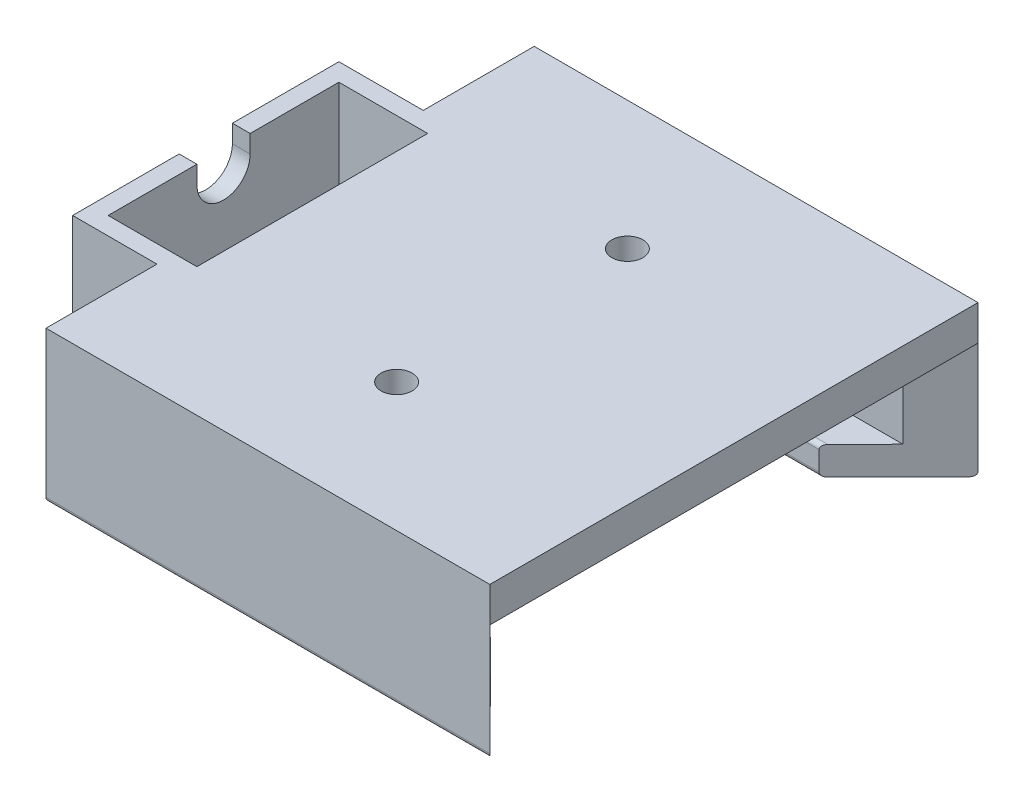
SolidWorks part; units mm, degrees
ref_plane "Спереди" through (0, 0, 0) normal (0, 0, 1) x (1, 0, 0)
ref_plane "Сверху" through (0, 0, 0) normal (0, 1, 0) x (1, 0, 0)
ref_plane "Справа" through (0, 0, 0) normal (1, 0, 0) x (0, 0, -1)
other "Configuration Table"
sketch "Эскиз1" plane through (0, 0, 0) normal (0, 1, 0) x (1, 0, 0)
  line L1 (-25, 27.5) -> (25, 27.5)
  line L2 (-25, 27.5) -> (-25, -27.5)
  line L3 (-25, -27.5) -> (25, -27.5)
  line L4 (25, 27.5) -> (25, -27.5)
  line L5 (-25, 27.5) -> (25, -27.5) construction
  line L6 (-25, -27.5) -> (25, 27.5) construction
  point P0 (0, 0)
  dimension "D1" = 55
  dimension "D2" = 50
extrude "Бобышка-Вытянуть1" add sketch "Эскиз1" along normal blind 6
sketch "Эскиз2" plane through (0, 0, 0) normal (0, -1, 0) x (1, 0, 0)
  line L0 (23.3173, 0) -> (43.7348, 0) construction
  line L1 (-25, 15) -> (-10, 15)
  line L2 (-25, 15) -> (-25, -15)
  line L3 (-25, -15) -> (-10, -15)
  line L4 (-10, 15) -> (-10, -15)
  line L5 (-25, -27.5) -> (-25, 27.5) construction
  line L6 (25, 27.5) -> (25, -27.5) construction
  dimension "D1" = 30
  dimension "D2" = 15
  dimension "D3" = 35
extrude "Бобышка-Вытянуть2" add sketch "Эскиз2" along normal blind 9
sketch "Эскиз3" plane through (0, -9, 0) normal (0, -1, 0) x (1, 0, 0)
  line L0 (-25, 15) -> (-25, -15) construction
  line L1 (-25, 12.5) -> (-10, 12.5)
  line L2 (-25, 12.5) -> (-25, 11.5)
  line L3 (-25, 11.5) -> (-10, 11.5)
  line L4 (-10, 12.5) -> (-10, 11.5)
  line L5 (-10, -15) -> (-10, 15) construction
  line L6 (-10, -15) -> (-10, 15) construction
  line L7 (-25, -11.5) -> (-10, -11.5)
  line L8 (-25, -11.5) -> (-25, -12.5)
  line L9 (-25, -12.5) -> (-10, -12.5)
  line L10 (-10, -11.5) -> (-10, -12.5)
  point P14 (-10, 0)
  point P15 (-10, -12)
  point P16 (-10, 12)
  dimension "D1" = 1
  dimension "D2" = 1
  dimension "D3" = 12
  dimension "D4" = 12
extrude "Вырез-Вытянуть1" cut sketch "Эскиз3" against normal blind 7
sketch "Эскиз4" plane through (0, 0, 0) normal (0, -1, 0) x (1, 0, 0)
  line L0 (-25, -27.5) -> (-25, -15) construction
  line L1 (-25, -23.25) -> (25, -23.25)
  line L2 (-25, -23.25) -> (-25, -27.5)
  line L3 (-25, -27.5) -> (25, -27.5)
  line L4 (25, -23.25) -> (25, -27.5)
  line L5 (25, 27.5) -> (25, -27.5) construction
  line L6 (-25, 15) -> (-25, 27.5) construction
  line L7 (-25, 23.25) -> (25, 23.25)
  line L8 (-25, 23.25) -> (-25, 27.5)
  line L9 (-25, 27.5) -> (25, 27.5)
  line L10 (25, 23.25) -> (25, 27.5)
  line L11 (0, 0) -> (45.721, 0) construction
  dimension "D1" = 46.5
extrude "Бобышка-Вытянуть3" add sketch "Эскиз4" along normal blind 9.5
sketch "Эскиз5" plane through (0, 0, 23.25) normal (0, 0, -1) x (-1, 0, 0)
  line L0 (25, 6) -> (25, -9.5) construction
  line L1 (-25, -9.5) -> (25, -9.5)
  line L2 (-25, -9.5) -> (-25, -5.8)
  line L3 (-25, -5.8) -> (25, -5.8)
  line L4 (25, -9.5) -> (25, -5.8)
  line L5 (-25, 0) -> (25, 0) construction
  dimension "D1" = 5.8
extrude "Бобышка-Вытянуть4" add sketch "Эскиз5" along normal blind 4.75
ref_plane "Плоскость1" through (0, 0, 0) normal (0, 0, 1) x (1, 0, 0)
mirror "Зеркальное отражение1" about plane through (0, 0, 0) normal (0, 0, 1) of "Бобышка-Вытянуть4"
sketch "Эскиз6" plane through (0, 0, 0) normal (0, -1, 0) x (1, 0, 0)
  line L0 (16.0877, -18.5) -> (25, -27.5)
  line L1 (25, -18.5) -> (-25, -18.5) construction
  line L2 (25, -27.5) -> (25, -18.5)
  line L3 (25, -18.5) -> (16.0877, -18.5)
  line L4 (8.525, 0) -> (-8.525, 0) construction
  line L5 (25, 18.5) -> (16.0877, 18.5)
  line L6 (25, 27.5) -> (25, 18.5)
  line L7 (16.0877, 18.5) -> (25, 27.5)
extrude "Вырез-Вытянуть2" cut sketch "Эскиз6" along normal blind 9.5
sketch "Эскиз7" plane through (-25, 0, 0) normal (-1, 0, 0) x (0, 0, 1)
  line L0 (-27.5, 6) -> (27.5, 6) construction
  line L1 (-15, -9) -> (15, -9)
  line L2 (-15, -9) -> (-15, 6)
  line L3 (-15, 6) -> (15, 6)
  line L4 (15, -9) -> (15, 6)
extrude "Бобышка-Вытянуть5" add sketch "Эскиз7" along normal blind 9.5
sketch "Эскиз8" plane through (0, 6, 0) normal (0, 1, 0) x (1, 0, 0)
  line L0 (-34.5, 15) -> (-25, 15) construction
  line L1 (-32.5, 13) -> (-22.5, 13)
  line L2 (-32.5, 13) -> (-32.5, -13)
  line L3 (-32.5, -13) -> (-22.5, -13)
  line L4 (-22.5, 13) -> (-22.5, -13)
  line L5 (-34.5, -15) -> (-34.5, 15) construction
  line L6 (-34.5, -15) -> (-25, -15) construction
  dimension "D1" = 2
  dimension "D2" = 2
  dimension "D3" = 2
  dimension "D4" = 12
extrude "Вырез-Вытянуть3" cut sketch "Эскиз8" against normal blind 10.5
sketch "Эскиз9" plane through (-34.5, 0, 0) normal (-1, 0, 0) x (0, 0, 1)
  line L0 (15, 6) -> (-15, 6) construction
  circle A0 centre (0, 6) radius 3
  dimension "D1" = 6
extrude "Вырез-Вытянуть4" cut sketch "Эскиз9" against normal blind 7.5
sketch "Эскиз10" plane through (0, 0, 0) normal (0, -1, 0) x (1, 0, 0)
  line L0 (8.525, 0) -> (-8.525, 0) construction
  circle A0 centre (0, 13) radius 1.75
  circle A1 centre (0, -13) radius 1.75
  dimension "D1" = 3.5
  dimension "D2" = 3.5
  dimension "D3" = 13
  dimension "D4" = 13
extrude "Вырез-Вытянуть5" cut sketch "Эскиз10" against normal blind 7.5
chamfer "Фаска1" distance 4 angle 45 2 edges at (0, 0, 11.25) (0, 0, -14.75)
sketch "Эскиз11" plane through (0, 6, 0) normal (0, 1, 0) x (1, 0, 0)
  line L16 (-34.5, 3) -> (-32.5, 3)
  line L17 (-32.5, 3) -> (-32.5, 13)
  line L18 (-32.5, 13) -> (-22.5, 13)
  line L19 (-22.5, 13) -> (-22.5, -13)
  line L20 (-22.5, -13) -> (-32.5, -13)
  line L21 (-32.5, -13) -> (-32.5, -3)
  line L22 (-32.5, -3) -> (-34.5, -3)
  line L23 (-34.5, -3) -> (-34.5, -15)
  line L24 (-34.5, -15) -> (-25, -15)
  line L25 (-25, -15) -> (-25, -27.5)
  line L26 (-25, -27.5) -> (25, -27.5)
  line L27 (25, -27.5) -> (25, 27.5)
  line L28 (25, 27.5) -> (-25, 27.5)
  line L29 (-25, 27.5) -> (-25, 15)
  line L30 (-25, 15) -> (-34.5, 15)
  line L31 (-34.5, 15) -> (-34.5, 3)
  line L32 (-34.5, 3) -> (-32.5, 3)
  line L33 (-32.5, 3) -> (-32.5, 13)
  line L34 (-32.5, 13) -> (-22.5, 13)
  line L35 (-22.5, 13) -> (-22.5, -13)
  line L36 (-22.5, -13) -> (-32.5, -13)
  line L37 (-32.5, -13) -> (-32.5, -3)
  line L38 (-32.5, -3) -> (-34.5, -3)
  line L39 (-34.5, -3) -> (-34.5, -15)
  line L40 (-34.5, -15) -> (-25, -15)
  line L41 (-25, -15) -> (-25, -27.5)
  line L42 (-25, -27.5) -> (25, -27.5)
  line L43 (25, -27.5) -> (25, 27.5)
  line L44 (25, 27.5) -> (-25, 27.5)
  line L45 (-25, 27.5) -> (-25, 15)
  line L46 (-25, 15) -> (-34.5, 15)
  line L47 (-34.5, 15) -> (-34.5, 3)
  circle A0 centre (0, 13) radius 1.75
  circle A1 centre (0, -13) radius 1.75
  dimension "D1" = 0
extrude "Бобышка-Вытянуть6" add sketch "Эскиз11" along normal blind 2
sketch "Эскиз12" plane through (0, -9.5, 0) normal (0, -1, 0) x (1, 0, 0)
  line L1 (-43.5949, 35.8115) -> (46.1446, 35.8115)
  line L2 (-43.5949, 35.8115) -> (-43.5949, -33.2837)
  line L3 (-43.5949, -33.2837) -> (46.1446, -33.2837)
  line L4 (46.1446, 35.8115) -> (46.1446, -33.2837)
extrude "Вырез-Вытянуть6" cut sketch "Эскиз12" against normal up to surface (0.5 mm away) up to face at (-19.0833, -9, 0)
chamfer "Фаска2" distance 7 angle 30 1 edges at (25, 0, 0) first distance on face at (0, 0, 18.75)
fillet "Скругление1" radius 0.5 6 edges at (-4.4561, -5.8, -18.5) (-4.4561, -5.8, 18.5) (-4.4561, -9, -18.5) (-4.4561, -9, 18.5) (0, -9, 27.5) (0, -9, -27.5)
